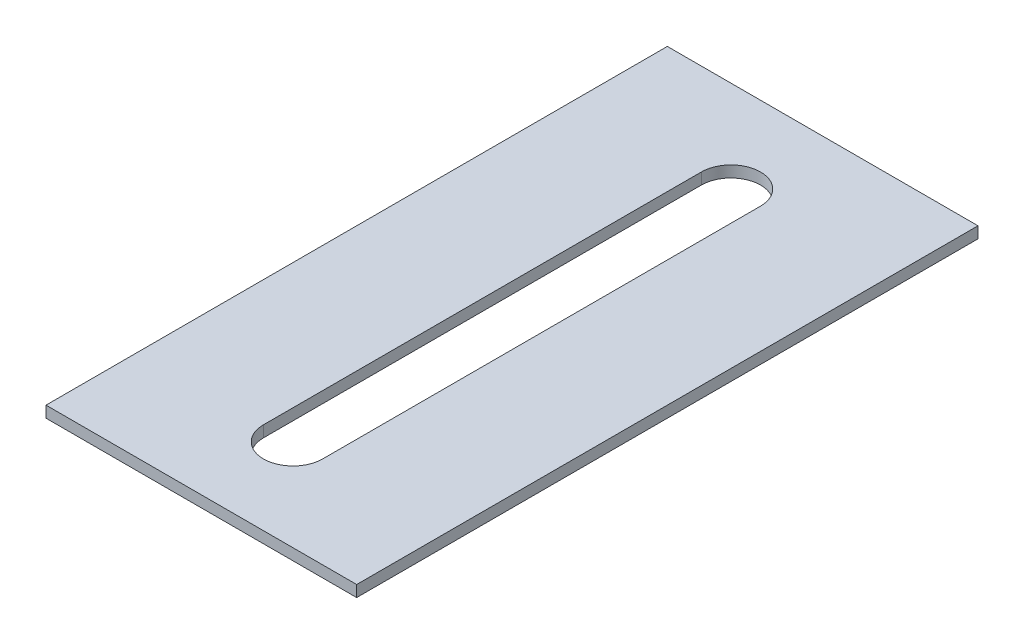
SolidWorks part; units mm, degrees
ref_plane "Front Plane" through (0, 0, 0) normal (0, 0, 1) x (1, 0, 0)
ref_plane "Top Plane" through (0, 0, 0) normal (0, 1, 0) x (1, 0, 0)
ref_plane "Right Plane" through (0, 0, 0) normal (1, 0, 0) x (0, 0, -1)
sketch "Sketch1" plane through (0, 0, 0) normal (0, 1, 0) x (1, 0, 0)
  line L0 (0, 35.2375) -> (0, -35.2375) construction
  line L1 (-25, 50) -> (25, 50)
  line L2 (-25, 50) -> (-25, -50)
  line L3 (-25, -50) -> (25, -50)
  line L4 (25, 50) -> (25, -50)
  line L5 (-25, 50) -> (25, -50) construction
  line L6 (-25, -50) -> (25, 50) construction
  line L7 (4.7625, 35.2375) -> (4.7625, -35.2375)
  line L8 (-4.7625, 35.2375) -> (-4.7625, -35.2375)
  arc A0 (4.7625, 35.2375) -> (-4.7625, 35.2375) centre (0, 35.2375) ccw
  arc A1 (-4.7625, -35.2375) -> (4.7625, -35.2375) centre (0, -35.2375) ccw
  point P0 (0, 0)
  point P8 (0, 0)
  point P13 (0, 40)
  point P14 (0, -40)
  dimension "D1" = 50
  dimension "D2" = 100
  dimension "D3" = 10
  dimension "D4" = 10
  dimension "D5" = 9.525
extrude "Boss-Extrude1" add sketch "Sketch1" along normal blind 0.9125 and the other way blind 0.9125
